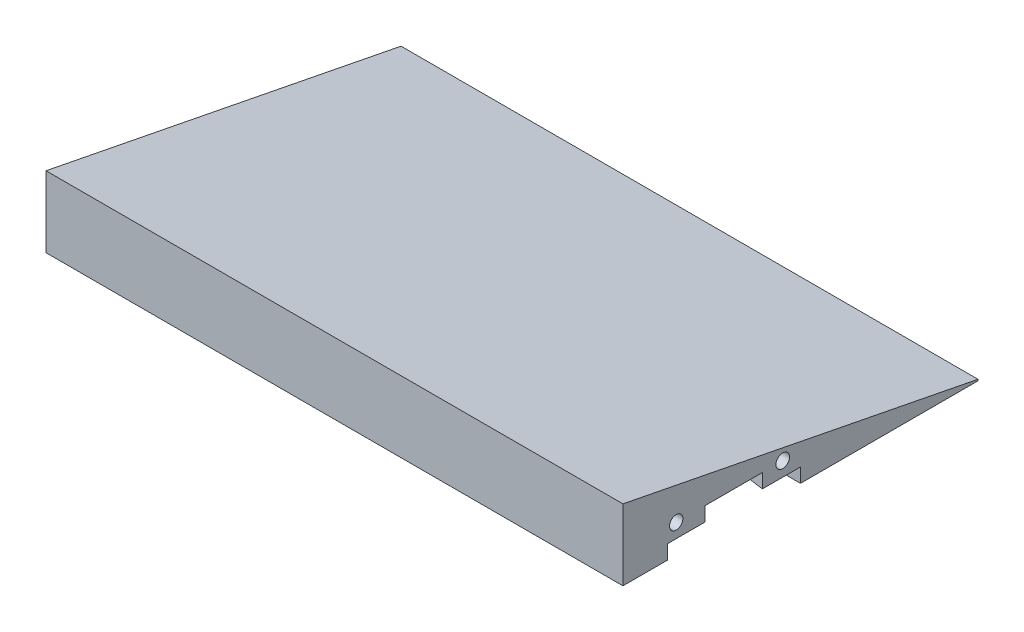
SolidWorks part; units mm, degrees
ref_plane "Front Plane" through (0, 0, 0) normal (0, 0, 1) x (1, 0, 0)
ref_plane "Top Plane" through (0, 0, 0) normal (0, 1, 0) x (1, 0, 0)
ref_plane "Right Plane" through (0, 0, 0) normal (1, 0, 0) x (0, 0, -1)
sketch "Sketch1" plane through (0, 0, 0) normal (1, 0, 0) x (0, 0, -1)
  line L0 (0, 0) -> (0, 20.32)
  line L1 (0, 20.32) -> (101.6, 0.4)
  line L2 (101.6, 0.4) -> (101.6, 0)
  line L3 (101.6, 0) -> (0, 0)
  dimension "D1" = 0.4
  dimension "D2" = 101.6
  dimension "D3" = 20.32
extrude "Boss-Extrude1" add sketch "Sketch1" along normal mid plane 391.16
sketch "Sketch2" plane through (195.58, 0, 0) normal (1, 0, 0) x (0, 0, -1)
  line L0 (0, 0) -> (101.6, 0) construction
  line L1 (101.6, 0.4) -> (0, 20.32) construction
  circle A0 centre (8.8764, 4.7625) radius 3.3147
  circle A1 centre (54.5964, 4.7625) radius 3.3147
  circle A2 centre (54.5964, 4.7625) radius 4.7625 construction
  circle A3 centre (8.8764, 4.7625) radius 4.7625 construction
  dimension "D1" = 45.72
  dimension "D2" = 6.6294
  dimension "D3" = 9.525
extrude "Cut-Extrude1" cut sketch "Sketch2" against normal blind 38.1
mirror "Mirror3" about plane through (0, 0, 0) normal (1, 0, 0) of "Cut-Extrude1"
sketch "Sketch3" plane through (-195.58, 0, 0) normal (-1, 0, 0) x (0, 0, 1)
  line L5 (0, 0) -> (-101.6, 0) construction
  line L6 (-50.8, 4.064) -> (-12.7, 4.064)
  line L7 (-50.8, 4.064) -> (-50.8, 0)
  line L8 (-50.8, 0) -> (-12.7, 0)
  line L9 (-12.7, 4.064) -> (-12.7, 0)
  line L10 (0, 20.32) -> (0, 0) construction
  dimension "D1" = 38.1
  dimension "D2" = 4.064
  dimension "D3" = 0
  dimension "D4" = 12.7
extrude "Cut-Extrude2" cut sketch "Sketch3" against normal through all
sketch "Sketch4" plane through (0, 0, 0) normal (0, -1, 0) x (1, 0, 0)
  line L0 (-144.6784, -50.8) -> (-146.004, -60.2323)
  line L1 (195.58, -50.8) -> (-195.58, -50.8) construction
  line L2 (-144.6784, -50.8) -> (-128.4828, -50.8)
  line L5 (-144.6784, -50.8) -> (-144.6784, -60.2323) construction
  line L6 (-128.4828, -50.8) -> (-127.1572, -60.2323)
  line L7 (-128.4828, -50.8) -> (-128.4828, -60.2323) construction
  line L8 (-144.6784, -60.2323) -> (-128.4828, -60.2323)
  line L9 (-144.6784, -60.2323) -> (-146.004, -60.2323)
  line L10 (-128.4828, -60.2323) -> (-127.1572, -60.2323)
  line L11 (-195.58, -50.8) -> (-195.58, -101.6) construction
  line L12 (-77.4796, -50.8) -> (-78.8053, -60.2323)
  line L13 (-77.4796, -60.2323) -> (-78.8053, -60.2323)
  line L14 (-77.4796, -60.2323) -> (-61.2841, -60.2323)
  line L15 (-61.2841, -60.2323) -> (-59.9585, -60.2323)
  line L16 (-61.2841, -50.8) -> (-59.9585, -60.2323)
  line L17 (-77.4796, -50.8) -> (-61.2841, -50.8)
  line L18 (-10.2809, -50.8) -> (-11.6065, -60.2323)
  line L19 (-10.2809, -60.2323) -> (-11.6065, -60.2323)
  line L20 (-10.2809, -60.2323) -> (5.9147, -60.2323)
  line L21 (5.9147, -60.2323) -> (7.2403, -60.2323)
  line L22 (5.9147, -50.8) -> (7.2403, -60.2323)
  line L23 (-10.2809, -50.8) -> (5.9147, -50.8)
  line L24 (56.9179, -50.8) -> (55.5922, -60.2323)
  line L25 (56.9179, -60.2323) -> (55.5922, -60.2323)
  line L26 (56.9179, -60.2323) -> (73.1134, -60.2323)
  line L27 (73.1134, -60.2323) -> (74.439, -60.2323)
  line L28 (73.1134, -50.8) -> (74.439, -60.2323)
  line L29 (56.9179, -50.8) -> (73.1134, -50.8)
  line L30 (124.1166, -50.8) -> (122.791, -60.2323)
  line L31 (124.1166, -60.2323) -> (122.791, -60.2323)
  line L32 (124.1166, -60.2323) -> (140.3122, -60.2323)
  line L33 (140.3122, -60.2323) -> (141.6378, -60.2323)
  line L34 (140.3122, -50.8) -> (141.6378, -60.2323)
  line L35 (124.1166, -50.8) -> (140.3122, -50.8)
  line L42 (-195.58, -31.75) -> (195.58, -31.75) construction
  line L43 (-195.58, -12.7) -> (-195.58, -50.8) construction
  line L44 (195.58, -12.7) -> (195.58, -50.8) construction
  line L52 (124.1166, -12.7) -> (140.3122, -12.7)
  line L53 (140.3122, -12.7) -> (141.6378, -3.2677)
  line L54 (140.3122, -3.2677) -> (141.6378, -3.2677)
  line L55 (124.1166, -3.2677) -> (140.3122, -3.2677)
  line L56 (124.1166, -3.2677) -> (122.791, -3.2677)
  line L57 (124.1166, -12.7) -> (122.791, -3.2677)
  line L58 (56.9179, -12.7) -> (73.1134, -12.7)
  line L59 (73.1134, -12.7) -> (74.439, -3.2677)
  line L60 (73.1134, -3.2677) -> (74.439, -3.2677)
  line L61 (56.9179, -3.2677) -> (73.1134, -3.2677)
  line L62 (56.9179, -3.2677) -> (55.5922, -3.2677)
  line L63 (56.9179, -12.7) -> (55.5922, -3.2677)
  line L64 (-10.2809, -12.7) -> (5.9147, -12.7)
  line L65 (5.9147, -12.7) -> (7.2403, -3.2677)
  line L66 (5.9147, -3.2677) -> (7.2403, -3.2677)
  line L67 (-10.2809, -3.2677) -> (5.9147, -3.2677)
  line L68 (-10.2809, -3.2677) -> (-11.6065, -3.2677)
  line L69 (-10.2809, -12.7) -> (-11.6065, -3.2677)
  line L70 (-77.4796, -12.7) -> (-61.2841, -12.7)
  line L71 (-61.2841, -12.7) -> (-59.9585, -3.2677)
  line L72 (-61.2841, -3.2677) -> (-59.9585, -3.2677)
  line L73 (-77.4796, -3.2677) -> (-61.2841, -3.2677)
  line L74 (-77.4796, -3.2677) -> (-78.8053, -3.2677)
  line L75 (-77.4796, -12.7) -> (-78.8053, -3.2677)
  line L76 (-144.6784, -12.7) -> (-128.4828, -12.7)
  line L77 (-128.4828, -12.7) -> (-127.1572, -3.2677)
  line L78 (-128.4828, -3.2677) -> (-127.1572, -3.2677)
  line L79 (-144.6784, -3.2677) -> (-128.4828, -3.2677)
  line L80 (-144.6784, -3.2677) -> (-146.004, -3.2677)
  line L81 (-144.6784, -12.7) -> (-146.004, -3.2677)
  dimension "D1" = 8
  dimension "D2" = 8
  dimension "D3" = 18.8468
  dimension "D4" = 9.525
  dimension "D5" = 50.9016
  dimension "D7" = 51.0032
  dimension "D6" = 5
extrude "Cut-Extrude3" cut sketch "Sketch4" against normal blind 4.064
sketch "Sketch7" plane through (195.58, 0, 0) normal (1, 0, 0) x (0, 0, -1)
  line L1 (0, 0) -> (101.6, 0)
  line L2 (0, 0) -> (0, 20.54)
  line L3 (0, 20.54) -> (101.6, 20.54)
  line L4 (101.6, 0) -> (101.6, 20.54)
extrude "Cut-Extrude5" cut sketch "Sketch7" against normal blind 226.06
sketch "Sketch9" plane through (0, 4.064, 0) normal (0, -1, 0) x (1, 0, 0)
  line L0 (-30.48, -23.495) -> (-39.9123, -22.1694)
  line L1 (-30.48, -50.8) -> (-30.48, -12.7) construction
  line L2 (-39.9123, -22.1694) -> (-39.9123, -41.2194)
  line L3 (-39.9123, -41.2194) -> (-30.48, -39.8938)
  line L4 (-30.48, -39.8938) -> (-30.48, -23.495)
  line L5 (-30.48, -23.495) -> (-39.9123, -23.495) construction
  line L6 (-30.48, -39.8938) -> (-39.9123, -39.8938) construction
  line L7 (-30.48, -12.7) -> (-61.2841, -12.7) construction
  dimension "D1" = 8
  dimension "D2" = 8
  dimension "D3" = 9.525
  dimension "D4" = 19.05
  dimension "D5" = 10.795
extrude "Cut-Extrude6" cut sketch "Sketch9" against normal blind 4.064
sketch "Sketch10" plane through (-30.48, 0, 0) normal (1, 0, 0) x (0, 0, -1)
  line L0 (0, 20.32) -> (0, 0) construction
  line L1 (23.495, 4.064) -> (12.7, 4.064) construction
  line L2 (50.8, 4.064) -> (39.8938, 4.064) construction
  circle A0 centre (15.24, 8.128) radius 1.905
  circle A1 centre (45.72, 8.128) radius 1.9499
  dimension "D5" = 3.81
  dimension "D6" = 3.8998
  dimension "D1" = 15.24
  dimension "D2" = 30.48
  dimension "D3" = 4.064
  dimension "D4" = 4.064
extrude "Cut-Extrude7" cut sketch "Sketch10" against normal blind 12.7
